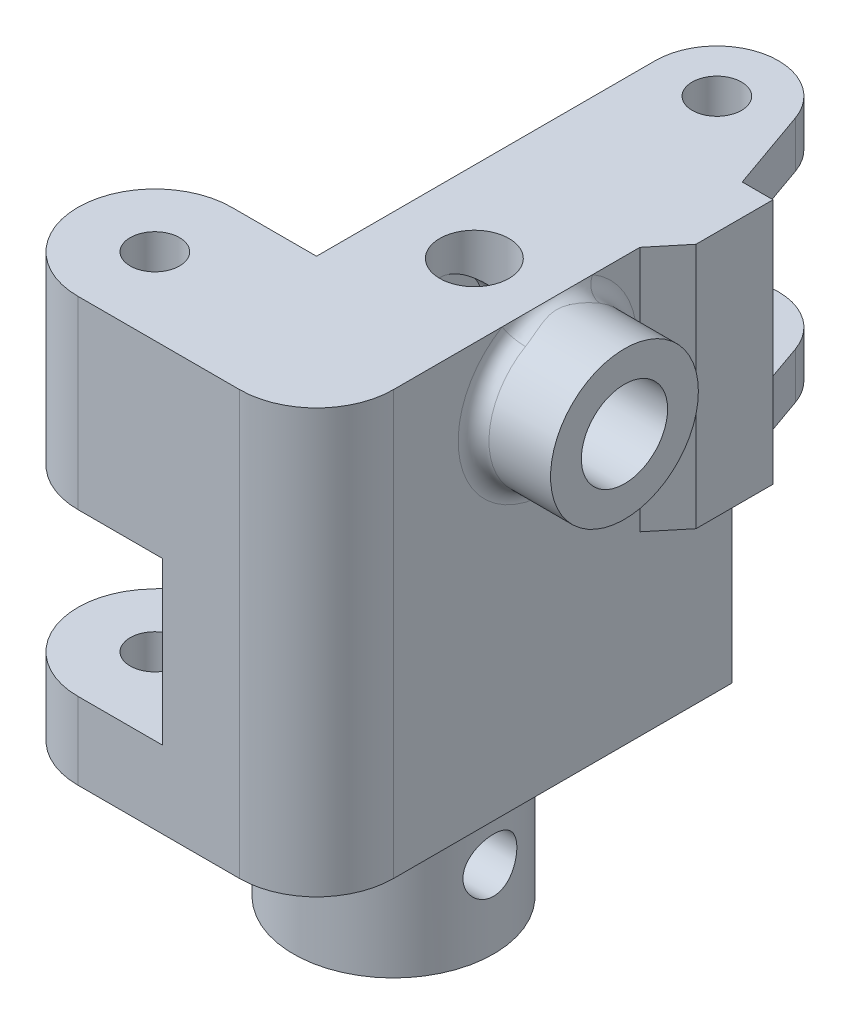
SolidWorks part; units mm, degrees
ref_plane "Front Plane" through (0, 0, 0) normal (0, 0, 1) x (1, 0, 0)
ref_plane "Top Plane" through (0, 0, 0) normal (0, 1, 0) x (1, 0, 0)
ref_plane "Right Plane" through (0, 0, 0) normal (1, 0, 0) x (0, 0, -1)
sketch "Sketch1" plane through (0, 0, 0) normal (0, 1, 0) x (1, 0, 0)
  line L0 (0, 0) -> (5.5, 0) construction
  line L1 (0, 5) -> (5.5, 5)
  line L2 (0, -5) -> (5.5, -5)
  line L3 (5.5, 5) -> (5.5, 22)
  line L4 (5.5, -5) -> (15.5, -5)
  line L6 (5.5, 22) -> (15.5, 22)
  line L7 (15.5, -5) -> (15.5, 22)
  line L8 (5.5, 20) -> (15.5, 20) construction
  arc A0 (0, 5) -> (0, -5) centre (0, 0) ccw
  circle A2 centre (0, 0) radius 1.6
  circle A3 centre (5.5, 10) radius 39 construction
  dimension "D1" = 5
  dimension "D2" = 3.2
  dimension "D5" = 78
  dimension "D3" = 5.5
  dimension "D4" = 10
  dimension "D6" = 10
  dimension "D7" = 10
  dimension "D8" = 2
extrude "Boss-Extrude1" add sketch "Sketch1" along normal blind 5
sketch "Sketch2" plane through (0, 5, 0) normal (0, 1, 0) x (1, 0, 0)
  line L1 (5.5, 22) -> (15.5, 22)
  line L2 (5.5, 22) -> (5.5, -5)
  line L3 (5.5, -5) -> (15.5, -5)
  line L4 (15.5, 22) -> (15.5, -5)
extrude "Boss-Extrude2" add sketch "Sketch2" along normal blind 10.5
sketch "Sketch3" plane through (0, 15.5, 0) normal (0, 1, 0) x (1, 0, 0)
  line L0 (5.5, 5) -> (15.5, 5)
  line L3 (5.5, -5) -> (5.5, 5)
  line L4 (5.5, 22) -> (5.5, -5)
  line L5 (5.5, -5) -> (15.5, -5)
  line L6 (15.5, -5) -> (15.5, 22)
  line L7 (15.5, 22) -> (5.5, 22)
  line L9 (5.5, -5) -> (15.5, -5)
  line L10 (15.5, -5) -> (15.5, 5)
  line L12 (5.5, 5) -> (0, 5)
  line L13 (0, -5) -> (5.5, -5)
  line L15 (5.5, 5) -> (0, 5)
  line L16 (0, -5) -> (5.5, -5)
  arc A1 (0, 5) -> (0, -5) centre (0, 0) ccw
  arc A2 (0, 5) -> (0, -5) centre (0, 0) ccw
  circle A4 centre (0, 0) radius 1.6
  dimension "D3" = 3.2
  dimension "D1" = 0
  dimension "D2" = 0
extrude "Boss-Extrude3" add sketch "Sketch3" along normal blind 5
fillet "Fillet1" radius 5 1 edges at (15.5, 10.25, 5)
sketch "Sketch4" plane through (15.5, 0, 0) normal (1, 0, 0) x (0, 0, -1)
  line L0 (1.75, 20.5) -> (-1.75, 20.5) construction
  line L1 (1.75, 20.5) -> (-1.75, 20.5)
  line L2 (0, 20.5) -> (0, 10.25) construction
  line L3 (0, 20.5) -> (0, 0) construction
  line L4 (0, 10.25) -> (20, 10.25) construction
  circle A0 centre (20, 10.25) radius 2.8 construction
  dimension "D2" = 5.6
  dimension "D1" = 20
extrude "Cut-Extrude1" [suppressed] cut sketch "Sketch4" against normal through all contours A0
sketch "Sketch5" plane through (0, 0, 0) normal (0, -1, 0) x (1, 0, 0)
  line L0 (5.5, -22) -> (5.5, -5) construction
  circle A0 centre (5.5, -10) radius 6.5
  circle A1 centre (0, 0) radius 1.6 construction
  circle A2 centre (0, 0) radius 1.6 construction
  circle A3 centre (5.5, -10) radius 2.5
  dimension "D2" = 13
  dimension "D3" = 5
  dimension "D1" = 10
extrude "Boss-Extrude4" add sketch "Sketch5" along normal blind 11
sketch "Sketch6" plane through (0, 0, 0) normal (0, 1, 0) x (1, 0, 0)
  line L3 (5.5, 12.5) -> (5.5, 16.5)
  line L4 (1.3467, 5) -> (5.5, 5)
  line L5 (5.5, 5) -> (5.5, 7.5)
  line L6 (5.5, 12.5) -> (5.5, 16.5)
  line L7 (1.3467, 5) -> (5.5, 5)
  line L8 (5.5, 5) -> (5.5, 7.5)
  arc A2 (5.5, 16.5) -> (1.3467, 5) centre (5.5, 10) ccw
  arc A3 (5.5, 12.5) -> (5.5, 7.5) centre (5.5, 10) ccw
  arc A4 (5.5, 16.5) -> (1.3467, 5) centre (5.5, 10) ccw
  arc A5 (5.5, 12.5) -> (5.5, 7.5) centre (5.5, 10) ccw
  dimension "D1" = 0
extrude "Boss-Extrude5" add sketch "Sketch6" along normal up to surface (5 mm away) up to face at (1.5, 5, 0)
sketch "Sketch7" plane through (0, 0, 0) normal (1, 0, 0) x (0, 0, -1)
  line L0 (10, -11) -> (10, -6) construction
  line L1 (3.5, -11) -> (16.5, -11) construction
  circle A0 centre (10, -6) radius 1.75
  dimension "D1" = 3.5
  dimension "D2" = 5
extrude "Cut-Extrude2" cut sketch "Sketch7" against normal through all both and the other way through all
sketch "Sketch8" [suppressed] plane through (15.5, 0, 0) normal (1, 0, 0) x (0, 0, -1)
  circle A0 centre (13.5, 10.25) radius 1.6
  circle A1 centre (26.5, 10.25) radius 1.6
  circle A2 centre (20, 10.25) radius 2.8 construction
  circle A3 centre (20, 10.25) radius 2.8 construction
  dimension "D2" = 3.2
  dimension "D3" = 3.2
  dimension "D1" = 6.5
  dimension "D4" = 6.5
extrude "Cut-Extrude3" [suppressed] cut sketch "Sketch8" against normal blind 8
fillet "Fillet2" [suppressed] radius 5
chamfer "Chamfer1" [suppressed] distance 1 angle 45
fillet "Fillet3" radius 5 1 edges at (10.5, 15.5, -5)
sketch "Sketch9" plane through (5.5, 0, 0) normal (-1, 0, 0) x (0, 0, 1)
  line L0 (-22, 15.5) -> (-10, 15.5) construction
  line L1 (-22, 15.5) -> (-5, 15.5)
  line L2 (-22, 15.5) -> (-22, 27.5)
  line L3 (-22, 27.5) -> (-5, 27.5)
  line L4 (-5, 15.5) -> (-5, 27.5)
  line L5 (-5, 20.5) -> (-5, 15.5) construction
  line L7 (-22, 15.5) -> (-22, 0) construction
  dimension "D1" = 12
extrude "Boss-Extrude6" add sketch "Sketch9" against normal up to surface (10 mm away) up to face at (15.5, 11.8274, -9.6607)
fillet "Fillet4" [suppressed] radius 4
fillet "Fillet5" [suppressed] radius 2
sketch "Sketch10" [suppressed] plane through (0, 27.5, 0) normal (0, 1, 0) x (1, 0, 0)
  line L0 (10.5, 11.1) -> (10.5, 7) construction
  line L1 (5.5, 7) -> (15.5, 7) construction
  line L2 (10.5, 11.1) -> (5.5, 11.1) construction
  line L3 (5.5, 7) -> (5.5, 15.2) construction
  line L5 (9.5, 13.35) -> (11.5, 13.35) construction
  line L6 (9.5, 13.35) -> (9.5, 8.85) construction
  line L7 (9.5, 8.85) -> (11.5, 8.85) construction
  line L8 (11.5, 13.35) -> (11.5, 8.85) construction
  line L9 (9.5, 13.35) -> (11.5, 8.85) construction
  line L10 (9.5, 8.85) -> (11.5, 13.35) construction
  circle A1 centre (10.5, 11.1) radius 2
  dimension "D1" = 4.5
  dimension "D3" = 4
  dimension "D2" = 2
extrude "Cut-Extrude4" [suppressed] cut sketch "Sketch10" against normal blind 10
sketch "Sketch11" plane through (15.5, 0, 0) normal (1, 0, 0) x (0, 0, -1)
  line L0 (10, 22.5) -> (10, 27.5) construction
  line L2 (5, 27.5) -> (5, 20.5) construction
  circle A0 centre (10, 22.5) radius 2.8
  dimension "D1" = 5.6
  dimension "D2" = 5
  dimension "D3" = 5
extrude "Cut-Extrude5" cut sketch "Sketch11" against normal blind 7
sketch "Sketch12" plane through (15.5, 0, 0) normal (1, 0, 0) x (0, 0, -1)
  circle A0 centre (10, 22.5) radius 2.8 construction
  circle A1 centre (10, 22.5) radius 2.8
  circle A2 centre (10, 22.5) radius 4.8
  dimension "D1" = 2
extrude "Boss-Extrude7" add sketch "Sketch12" along normal blind 5
chamfer "Chamfer2" distance 3 angle 45 1 edges at (5.5, -11, -12.5)
chamfer "Chamfer3" distance 3 angle 45 1 edges at (5.5, 0, -10)
fillet "Fillet6" radius 2 1 edges at (3, 5, -10)
sketch "Sketch13" [suppressed] plane through (5.5, 0, 0) normal (-1, 0, 0) x (0, 0, 1)
  line L0 (-26, 15.5) -> (-17.2, 15.5) construction
  line L1 (-26, 0) -> (-37, 0)
  line L2 (-26, 0) -> (-26, 15.5)
  line L3 (-26, 15.5) -> (-37, 15.5)
  line L4 (-41, 4) -> (-41, 11.5)
  line L5 (-16.5, 5) -> (-16.5, 0) construction
  circle A0 centre (-35, 10.25) radius 2.8
  arc A3 (-37, 0) -> (-41, 4) centre (-37, 4) cw
  arc A4 (-37, 15.5) -> (-41, 11.5) centre (-37, 11.5) ccw
  dimension "D1" = 5.6
  dimension "D3" = 4
  dimension "D2" = 18.5
  dimension "D4" = 6
  dimension "D5" = 10.25
extrude "Boss-Extrude8" [suppressed] add sketch "Sketch13" against normal up to surface (10 mm away)
sketch "Sketch14" plane through (0, 20.5, 0) normal (0, 1, 0) x (1, 0, 0)
  line L4 (0, -5) -> (10.5, -5)
  line L5 (15.5, 0) -> (15.5, 5)
  line L6 (15.5, 5) -> (5.5, 5)
  line L7 (5.5, 5) -> (0, 5)
  line L8 (0, -5) -> (10.5, -5)
  line L9 (15.5, 0) -> (15.5, 5)
  line L11 (5.5, 5) -> (0, 5)
  line L13 (15.5, 5) -> (5.5, 5)
  arc A2 (10.5, -5) -> (15.5, 0) centre (10.5, 0) ccw
  arc A3 (0, 5) -> (0, -5) centre (0, 0) ccw
  arc A4 (10.5, -5) -> (15.5, 0) centre (10.5, 0) ccw
  arc A5 (0, 5) -> (0, -5) centre (0, 0) ccw
  circle A6 centre (0, 0) radius 1.6
  dimension "D2" = 3.2
  dimension "D1" = 0
extrude "Boss-Extrude9" add sketch "Sketch14" along normal up to surface (7 mm away) up to face at (10.5, 27.5, -13.5)
fillet "Fillet7" radius 10 1 edges at (1.3467, 2.5, -5)
fillet "Fillet8" [suppressed] radius 5
sketch "Sketch15" plane through (0, 27.5, 0) normal (0, 1, 0) x (1, 0, 0)
  line L0 (8.5, 7.2) -> (8.5, 12.8) construction
  line L1 (8.5, 7.2) -> (8.5, 12.8) construction
  line L2 (10.75, 10) -> (8.5, 10) construction
  circle A0 centre (10.75, 10) radius 2.25
  dimension "D1" = 4.5
extrude "Cut-Extrude6" cut sketch "Sketch15" against normal blind 10
fillet "Fillet9" radius 1 1 edges at (15.5, 22.5, -5.2)
sketch "Sketch16" plane through (0, 27.5, 0) normal (0, 1, 0) x (1, 0, 0)
  line L0 (5.5, 22) -> (5.5, 27)
  line L1 (13.2732, 28.3278) -> (15.5, 22)
  line L2 (5.5, 22) -> (15.5, 22)
  circle A0 centre (9.5, 27) radius 1.6
  arc A1 (13.2732, 28.3278) -> (5.5, 27) centre (9.5, 27) ccw
  dimension "D1" = 3.2
  dimension "D2" = 8
  dimension "D3" = 5
extrude "Boss-Extrude10" add sketch "Sketch16" against normal blind 16
ref_plane "Plane1" through (0, 19.5, 0) normal (0, 1, 0) x (1, 0, 0)
sketch "Sketch17" plane through (0, 19.5, 0) normal (0, 1, 0) x (1, 0, 0)
  line L0 (15.5, 22) -> (5.5, 22)
  line L1 (5.5, 5) -> (5.5, 27) construction
  line L9 (15.5, 12.9394) -> (15.5, 22)
  line L10 (15.5, 22) -> (13.2732, 28.3278)
  line L11 (5.5, 27) -> (5.5, 5)
  line L12 (5.5, 5) -> (0, 5)
  line L13 (0, -5) -> (10.5, -5)
  line L14 (15.5, 0) -> (15.5, 7.0606)
  line L15 (15.5, 7.0606) -> (15.5, 12.9394)
  line L17 (15.5, 22) -> (13.2732, 28.3278)
  line L18 (5.5, 27) -> (5.5, 22)
  arc A3 (13.2732, 28.3278) -> (5.5, 27) centre (9.5, 27) ccw
  arc A4 (0, 5) -> (0, -5) centre (0, 0) ccw
  arc A5 (10.5, -5) -> (15.5, 0) centre (10.5, 0) ccw
  arc A6 (13.2732, 28.3278) -> (5.5, 27) centre (9.5, 27) ccw
  dimension "D1" = 0
extrude "Cut-Extrude7" cut sketch "Sketch17" against normal blind 5 and the other way blind 5
sketch "Sketch18" plane through (0, 27.5, 0) normal (0, 1, 0) x (1, 0, 0)
  line L0 (15.5, 22) -> (13.2732, 28.3278) construction
  line L1 (15.1481, 23) -> (17.1481, 23)
  line L2 (15.1481, 23) -> (15.1481, 18)
  line L4 (17.1481, 23) -> (17.1481, 18)
  line L5 (17.1481, 18) -> (15.5, 16)
  line L6 (15.5, 22) -> (15.5, 12.9394) construction
  line L7 (15.5, 16) -> (15.1481, 18)
  dimension "D1" = 1
  dimension "D2" = 2
  dimension "D3" = 2
  dimension "D4" = 4
extrude "Boss-Extrude11" add sketch "Sketch18" against normal up to surface (16 mm away) up to face at (9.5, 11.5, -25.4)
